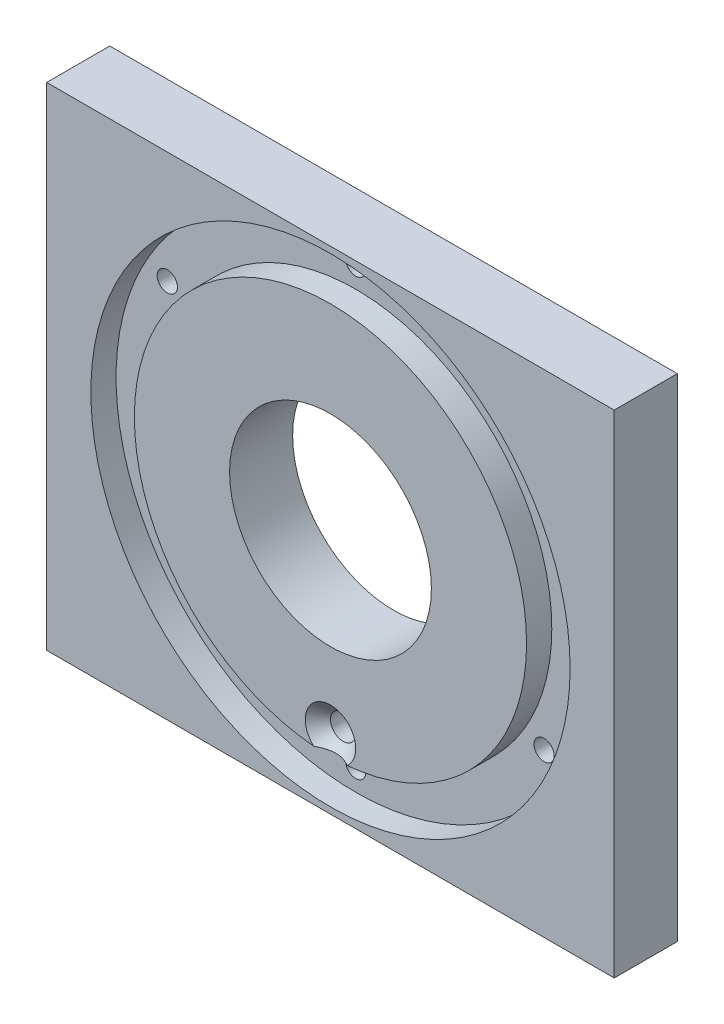
SolidWorks part; units mm, degrees
ref_plane "前视基准面" through (0, 0, 0) normal (0, 0, 1) x (1, 0, 0)
ref_plane "上视基准面" through (0, 0, 0) normal (0, 1, 0) x (1, 0, 0)
ref_plane "右视基准面" through (0, 0, 0) normal (1, 0, 0) x (0, 0, -1)
sketch "草图1" plane through (0, 0, 0) normal (0, 0, 1) x (1, 0, 0)
  line L1 (-45, -39) -> (45, -39)
  line L2 (-45, -39) -> (-45, 39)
  line L3 (-45, 39) -> (45, 39)
  line L4 (45, -39) -> (45, 39)
  line L5 (-45, -39) -> (45, 39) construction
  line L6 (-45, 39) -> (45, -39) construction
  circle A0 centre (0, 0) radius 16
  point P0 (0, 0)
  dimension "D3" = 32
  dimension "D1" = 90
  dimension "D2" = 78
extrude "凸台-拉伸1" add sketch "草图1" along normal blind 10
sketch "草图2" plane through (0, 0, 10) normal (0, 0, 1) x (1, 0, 0)
  circle A0 centre (0, 0) radius 31.1
  circle A1 centre (0, 0) radius 38
  dimension "D1" = 76
  dimension "D2" = 62.2
extrude "切除-拉伸1" cut sketch "草图2" against normal blind 4
hole_wizard "打孔尺寸(%根据)内六角圆柱头螺钉的类型1" positions "草图4" profile "草图3" counterbore size "M3" standard "GB"
sketch "草图4" plane through (0, 0, 0) normal (0, 0, -1) x (-1, 0, 0)
  circle A0 centre (0, 0) radius 34.5 construction
  point P0 (0, 34.5)
  point P10 (29.8779, 17.25)
  point P11 (29.8779, -17.25)
  point P12 (0, -34.5)
  point P13 (-29.8779, -17.25)
  point P14 (-29.8779, 17.25)
  dimension "D1" = 34.5
  dimension "D2" = 6
sketch "草图3" plane through (0, 34.5, 0) normal (1, 0, 0) x (0, 1, 0)
  line L0 (0, 0) -> (0, 9.4614)
  line L1 (0, 9.4614) -> (1.6, 8.5)
  line L2 (1.6, 8.5) -> (1.6, 3.4)
  line L3 (1.6, 3.4) -> (3, 3.4)
  line L4 (3, 3.4) -> (3, 0)
  line L5 (3, 0) -> (0, 0)
  line L10 (0, 9.4614) -> (-1.6, 8.5) construction
  line L11 (0, -6.35) -> (0, 107.95) construction
  dimension "孔直径" = 3.2
  dimension "孔深度" = 8.5
  dimension "柱形沉头孔直径" = 6
  dimension "柱形沉头孔深度" = 3.4
  dimension "导头角度" = 118
hole_wizard "Ø4.0 (4) 直径孔1" positions "草图7" profile "草图8" hole size "Ø4.0" standard "GB" end condition up to next
sketch "草图7" plane through (0, 0, 0) normal (0, 0, -1) x (-1, 0, 0)
  point P0 (0, -28)
  dimension "D1" = 28
sketch "草图8" plane through (0, -28, 0) normal (1, 0, 0) x (0, 1, 0)
  line L0 (0, 0) -> (0, 10)
  line L1 (0, 10) -> (2, 10)
  line L2 (2, 10) -> (2, 0)
  line L5 (2, 0) -> (0, 0)
  line L11 (0, -6.35) -> (0, 107.95) construction
  dimension "通孔孔直径" = 4
  dimension "通孔孔深度" = 10
chamfer "倒角1" distance 2 angle 45 2 edges at (-2, -28, 0) (-2, -28, 10)
